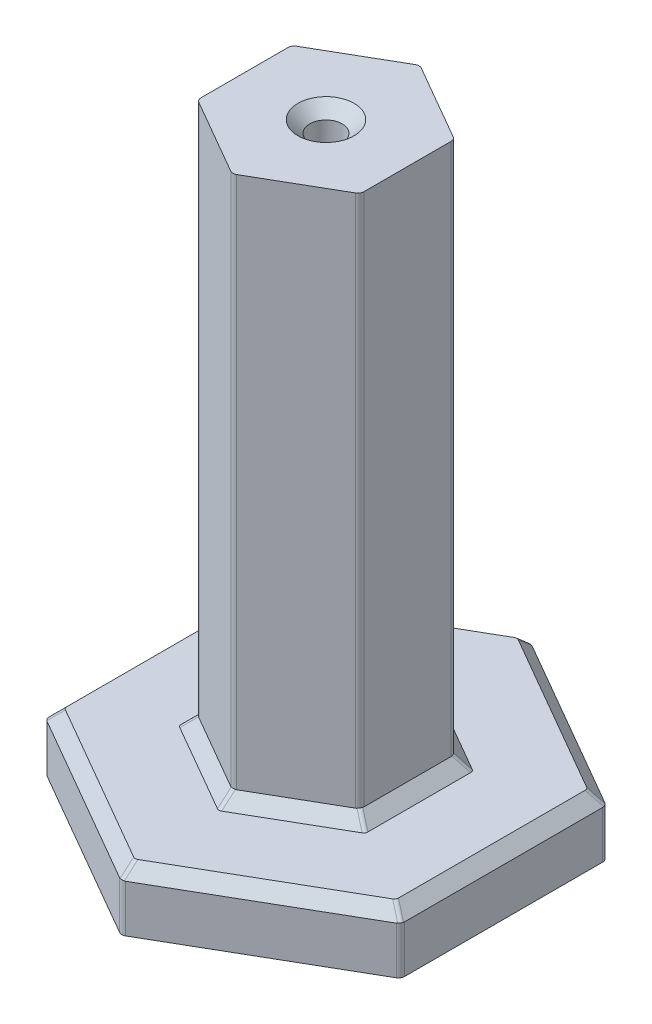
SolidWorks part; units mm, degrees
note: The reader was unsure of these and kept them because the rebuilt part matched: shared geometry of "Sketch2<3>".
ref_plane "Front Plane" through (0, 0, 0) normal (0, 0, 1) x (1, 0, 0)
ref_plane "Top Plane" through (0, 0, 0) normal (0, 1, 0) x (1, 0, 0)
ref_plane "Right Plane" through (0, 0, 0) normal (1, 0, 0) x (0, 0, -1)
sketch "Sketch2" plane through (0, 0, 0) normal (0, 1, 0) x (1, 0, 0)
  line L1 (0, -7.9386) -> (6.875, -3.9693)
  line L2 (6.875, -3.9693) -> (6.875, 3.9693)
  line L3 (6.875, 3.9693) -> (0, 7.9386)
  line L4 (0, 7.9386) -> (-6.875, 3.9693)
  line L5 (-6.875, 3.9693) -> (-6.875, -3.9693)
  line L6 (-6.875, -3.9693) -> (0, -7.9386)
  line L7 (0, -17.3205) -> (15, -8.6603)
  line L8 (15, -8.6603) -> (15, 8.6603)
  line L9 (15, 8.6603) -> (0, 17.3205)
  line L10 (0, 17.3205) -> (-15, 8.6603)
  line L11 (-15, 8.6603) -> (-15, -8.6603)
  line L12 (-15, -8.6603) -> (0, -17.3205)
  circle A0 centre (0, 0) radius 6.875 construction
  circle A1 centre (0, 0) radius 15 construction
  dimension "D1" = 13.75
  dimension "D2" = 30
extrude "Boss-Extrude1" add sketch "Sketch2" along normal blind 51 contours L5 L6 L1 L2 L3 L4
extrude "Boss-Extrude2" add sketch "Sketch2<3>" along normal blind 5
sketch "Sketch2<3>" plane through (0, 0, 0) normal (0, 1, 0) x (1, 0, 0) same geometry as "Sketch2"
sketch "Sketch5" plane through (0, 51, 0) normal (0, 1, 0) x (1, 0, 0)
  circle A1 centre (0, 0) radius 1.375
  dimension "D2" = 2.75
extrude "Cut-Extrude2" cut sketch "Sketch5" against normal blind 15 contours A1
chamfer "Chamfer1" distance 1 angle 45 13 edges at (0, 51, 1.375) (6.875, 5, 0) (3.4375, 5, -5.9539) (-3.4375, 5, -5.9539) (-6.875, 5, 0) (-3.4375, 5, 5.9539) (3.4375, 5, 5.9539) (-15, 5, 0) (-7.5, 5, -12.9904) (7.5, 5, -12.9904) (15, 5, 0) (7.5, 5, 12.9904) (-7.5, 5, 12.9904)
fillet "Fillet2" radius 0.5 24 edges at (0, 4.5, -16.7432) (-14.5, 4.5, 8.3716) (-14.5, 4.5, -8.3716) (0, 5.5, -8.5159) (-7.375, 5.5, -4.258) (-7.375, 5.5, 4.258) (7.375, 5.5, -4.258) (14.5, 4.5, -8.3716) (14.5, 4.5, 8.3716) (7.375, 5.5, 4.258) (0, 4.5, 16.7432) (0, 5.5, 8.5159) (15, 2, 8.6603) (0, 2, 17.3205) (-15, 2, 8.6603) (15, 2, -8.6603) (0, 2, -17.3205) (-15, 2, -8.6603) (-6.875, 28.5, 3.9693) (-6.875, 28.5, -3.9693) (0, 28.5, -7.9386) (6.875, 28.5, -3.9693) (6.875, 28.5, 3.9693) (0, 28.5, 7.9386)
